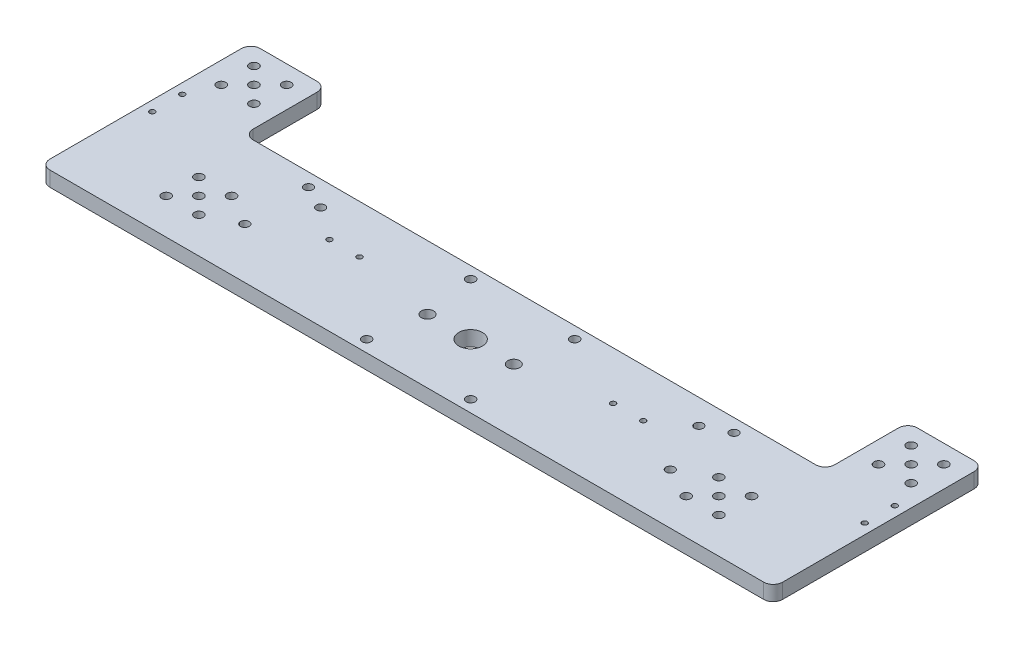
SolidWorks part; units mm, degrees
ref_plane "Front Plane" through (0, 0, 0) normal (0, 0, 1) x (1, 0, 0)
ref_plane "Top Plane" through (0, 0, 0) normal (0, 1, 0) x (1, 0, 0)
ref_plane "Right Plane" through (0, 0, 0) normal (1, 0, 0) x (0, 0, -1)
sketch "Sketch1" plane through (0, 0, 0) normal (0, 1, 0) x (1, 0, 0)
  line L1 (-155, -27) -> (155, -27)
  line L2 (-155, -27) -> (-155, 27)
  line L3 (-123, 27) -> (123, 27)
  line L4 (155, -27) -> (155, 27)
  line L5 (-155, -27) -> (155, 27) construction
  line L6 (-155, 27) -> (155, -27) construction
  line L7 (-123, 62) -> (-155, 62)
  line L8 (-123, 62) -> (-123, 27)
  line L10 (-155, 62) -> (-155, 27)
  line L11 (-123, 62) -> (-155, 27) construction
  line L12 (-123, 27) -> (-155, 62) construction
  line L13 (123, 62) -> (155, 62)
  line L14 (123, 62) -> (123, 27)
  line L16 (155, 62) -> (155, 27)
  line L17 (123, 62) -> (155, 27) construction
  line L18 (123, 27) -> (155, 62) construction
  point P0 (0, 0)
  point P6 (-139, 44.5)
  point P7 (139, 44.5)
  dimension "D1" = 310
  dimension "D2" = 32
  dimension "D3" = 35
  dimension "D4" = 54
extrude "Boss-Extrude1" add sketch "Sketch1" along normal blind 6.35
sketch "Sketch2" plane through (0, 6.35, 0) normal (0, 1, 0) x (1, 0, 0)
  circle A0 centre (0, 0) radius 5
  dimension "D1" = 10
extrude "Cut-Extrude1" cut sketch "Sketch2" against normal through all
sketch "Sketch3" plane through (0, 6.35, 0) normal (0, 1, 0) x (1, 0, 0)
  line L0 (-110, -4.974) -> (110, -4.974) construction
  line L1 (22, -22) -> (-22, -22) construction
  line L2 (22, -22) -> (22, 22) construction
  line L3 (22, 22) -> (-22, 22) construction
  line L4 (-22, -22) -> (-22, 22) construction
  line L5 (22, -22) -> (-22, 22) construction
  line L6 (22, 22) -> (-22, -22) construction
  line L7 (-116.915, -11.889) -> (-103.085, -11.889) construction
  line L8 (-116.915, -11.889) -> (-116.915, 1.941) construction
  line L9 (-116.915, 1.941) -> (-103.085, 1.941) construction
  line L10 (-103.085, -11.889) -> (-103.085, 1.941) construction
  line L11 (-116.915, -11.889) -> (-103.085, 1.941) construction
  line L12 (-116.915, 1.941) -> (-103.085, -11.889) construction
  line L13 (116.915, -11.889) -> (103.085, -11.889) construction
  line L14 (116.915, -11.889) -> (116.915, 1.941) construction
  line L15 (116.915, 1.941) -> (103.085, 1.941) construction
  line L16 (103.085, -11.889) -> (103.085, 1.941) construction
  line L17 (116.915, -11.889) -> (103.085, 1.941) construction
  line L18 (116.915, 1.941) -> (103.085, -11.889) construction
  line L19 (-145.941, 40.435) -> (-132.111, 40.435) construction
  line L20 (-145.941, 40.435) -> (-145.941, 54.265) construction
  line L21 (-145.941, 54.265) -> (-132.111, 54.265) construction
  line L22 (-132.111, 40.435) -> (-132.111, 54.265) construction
  line L23 (-145.941, 40.435) -> (-132.111, 54.265) construction
  line L24 (-145.941, 54.265) -> (-132.111, 40.435) construction
  line L25 (132.111, 40.435) -> (145.941, 40.435) construction
  line L26 (132.111, 40.435) -> (132.111, 54.265) construction
  line L27 (132.111, 54.265) -> (145.941, 54.265) construction
  line L28 (145.941, 40.435) -> (145.941, 54.265) construction
  line L29 (132.111, 40.435) -> (145.941, 54.265) construction
  line L30 (132.111, 54.265) -> (145.941, 40.435) construction
  line L31 (-139.026, 47.35) -> (139.026, 47.35) construction
  point P0 (0, 0)
  point P6 (-110, -4.974)
  point P11 (110, -4.974)
  point P16 (-139.026, 47.35)
  point P21 (139.026, 47.35)
  point P26 (0, -4.974)
  point P32 (0, 47.35)
  dimension "D1" = 44
  dimension "D2" = 44
  dimension "D3" = 13.83
  dimension "D4" = 220
  dimension "D5" = 278.052
  dimension "D6" = 52.324
  dimension "D7" = 4.974
hole_wizard "#6 Clearance Hole1" positions "3DSketch2" profile "Sketch4" hole size "#6" standard "ANSI Inch"
sketch3d "3DSketch2"
  point P0 (-145.941, 6.35, -54.265)
  point P3 (-132.111, 6.35, -54.265)
  point P6 (-132.111, 6.35, -40.435)
  point P9 (-145.941, 6.35, -40.435)
  point P12 (-139.026, 6.35, -47.35)
  point P15 (-116.915, 6.35, -1.941)
  point P18 (-103.085, 6.35, -1.941)
  point P21 (-103.085, 6.35, 11.889)
  point P24 (-116.915, 6.35, 11.889)
  point P27 (-110, 6.35, 4.974)
  point P30 (-22, 6.35, -22)
  point P33 (22, 6.35, -22)
  point P36 (22, 6.35, 22)
  point P39 (-22, 6.35, 22)
  point P42 (103.085, 6.35, 11.889)
  point P45 (103.085, 6.35, -1.941)
  point P48 (116.915, 6.35, -1.941)
  point P51 (116.915, 6.35, 11.889)
  point P54 (110, 6.35, 4.974)
  point P57 (132.111, 6.35, -40.435)
  point P60 (139.026, 6.35, -47.35)
  point P63 (132.111, 6.35, -54.265)
  point P66 (145.941, 6.35, -54.265)
  point P69 (145.941, 6.35, -40.435)
sketch "Sketch4" plane through (-145.941, 6.35, -54.265) normal (1, 0, 0) x (0, 0, 1)
  line L0 (0, 0) -> (0, 11.1408)
  line L1 (0, 11.1408) -> (1.8986, 10)
  line L2 (1.8986, 10) -> (1.8986, 0)
  line L5 (1.8986, 0) -> (0, 0)
  line L10 (0, 11.1408) -> (-1.8987, 10) construction
  line L11 (0, -6.35) -> (0, 107.95) construction
  dimension "Hole Dia." = 3.7973
  dimension "Hole Depth" = 10
  dimension "Drill Angle" = 118
fillet "Fillet1" radius 4 8 edges at (155, 3.175, 27) (155, 3.175, -62) (123, 3.175, -62) (123, 3.175, -27) (-123, 3.175, -27) (-155, 3.175, 27) (-123, 3.175, -62) (-155, 3.175, -62)
sketch "Sketch5" plane through (0, 6.35, 0) normal (0, 1, 0) x (1, 0, 0)
  line L0 (-18.25, 0) -> (18.25, 0) construction
  point P5 (0, 0)
  dimension "D1" = 36.5
hole_wizard "#10 Clearance Hole1" positions "3DSketch3" profile "Sketch6" hole size "#10" standard "ANSI Inch"
sketch3d "3DSketch3"
  point P0 (-18.25, 6.35, 0)
  point P3 (18.25, 6.35, 0)
sketch "Sketch6" plane through (-18.25, 6.35, 0) normal (1, 0, 0) x (0, 0, 1)
  line L0 (0, 0) -> (0, 11.5338)
  line L1 (0, 11.5338) -> (2.5527, 10)
  line L2 (2.5527, 10) -> (2.5527, 0)
  line L5 (2.5527, 0) -> (0, 0)
  line L10 (0, 11.5338) -> (-2.5527, 10) construction
  line L11 (0, -6.35) -> (0, 107.95) construction
  dimension "Hole Dia." = 5.1054
  dimension "Hole Depth" = 10
  dimension "Drill Angle" = 118
sketch "Sketch7" plane through (0, 6.35, 0) normal (0, 1, 0) x (1, 0, 0)
  line L0 (119, 27) -> (-119, 27) construction
  line L1 (-90, 21.412) -> (90, 21.412) construction
  line L2 (-90, 21.412) -> (-90, -5.5374) construction
  line L3 (-90, -5.5374) -> (90, -5.5374) construction
  line L4 (90, 21.412) -> (90, -5.5374) construction
  line L5 (-90, 21.412) -> (90, -5.5374) construction
  line L6 (-90, -5.5374) -> (90, 21.412) construction
  line L7 (-80, 16.5352) -> (80, 16.5352) construction
  point P0 (0, 7.9373)
  point P12 (0, 16.5352)
  dimension "D1" = 26.9494
  dimension "D2" = 5.588
  dimension "D3" = 180
  dimension "D4" = 160
  dimension "D5" = 10.4648
hole_wizard "#6 Clearance Hole2" positions "Sketch8" profile "Sketch9" hole size "#6" standard "ANSI Inch" end condition through all
sketch "Sketch8" plane through (0, 6.35, 0) normal (0, 1, 0) x (-1, 0, 0)
  point P0 (90, -21.412)
  point P3 (90, 5.5374)
  point P6 (-90, 5.5374)
  point P9 (-90, -21.412)
  point P13 (80, -16.5352)
  point P16 (-80, -16.5352)
sketch "Sketch9" plane through (-90, 6.35, -21.412) normal (1, 0, 0) x (0, 0, 1)
  line L0 (0, 0) -> (0, 6.35)
  line L1 (0, 6.35) -> (1.8288, 6.35)
  line L2 (1.8288, 6.35) -> (1.8288, 0)
  line L5 (1.8288, 0) -> (0, 0)
  line L11 (0, -6.35) -> (0, 107.95) construction
  dimension "Thru Hole Dia." = 3.6576
  dimension "Thru Hole Depth" = 6.35
sketch "Sketch10" plane through (0, 6.35, 0) normal (0, 1, 0) x (1, 0, 0)
  line L0 (-150.71, 28.7) -> (-150.71, 16) construction
  line L2 (-66.35, 6.635) -> (-53.65, 6.635) construction
  circle A0 centre (-139.026, 47.35) radius 1.8987 construction
  circle A1 centre (-110, -4.974) radius 1.8987 construction
  point P3 (-150.71, 22.35)
  point P9 (-60, 6.635)
  dimension "D2" = 11.684
  dimension "D5" = 11.609
  dimension "D1" = 12.7
  dimension "D3" = 25
  dimension "D4" = 12.7
  dimension "D6" = 60
hole_wizard "Tap Drill for #4-40 Tap1" positions "3DSketch4" profile "Sketch11" hole size "#4-40" standard "ANSI Inch"
sketch3d "3DSketch4"
  point P0 (-150.71, 6.35, -28.7)
  point P3 (-150.71, 6.35, -16)
  point P6 (-66.35, 6.35, -6.635)
  point P9 (-53.65, 6.35, -6.635)
sketch "Sketch11" plane through (-150.71, 6.35, -28.7) normal (1, 0, 0) x (0, 0, 1)
  line L0 (0, 0) -> (0, 7.0292)
  line L1 (0, 7.0292) -> (1.1303, 6.35)
  line L2 (1.1303, 6.35) -> (1.1303, 0)
  line L5 (1.1303, 0) -> (0, 0)
  line L10 (0, 7.0292) -> (-1.1303, 6.35) construction
  line L11 (0, -6.35) -> (0, 107.95) construction
  dimension "Hole Dia." = 2.2606
  dimension "Hole Depth" = 6.35
  dimension "Drill Angle" = 118
mirror "Mirror1" about plane through (0, 0, 0) normal (1, 0, 0) of "Tap Drill for #4-40 Tap1"
